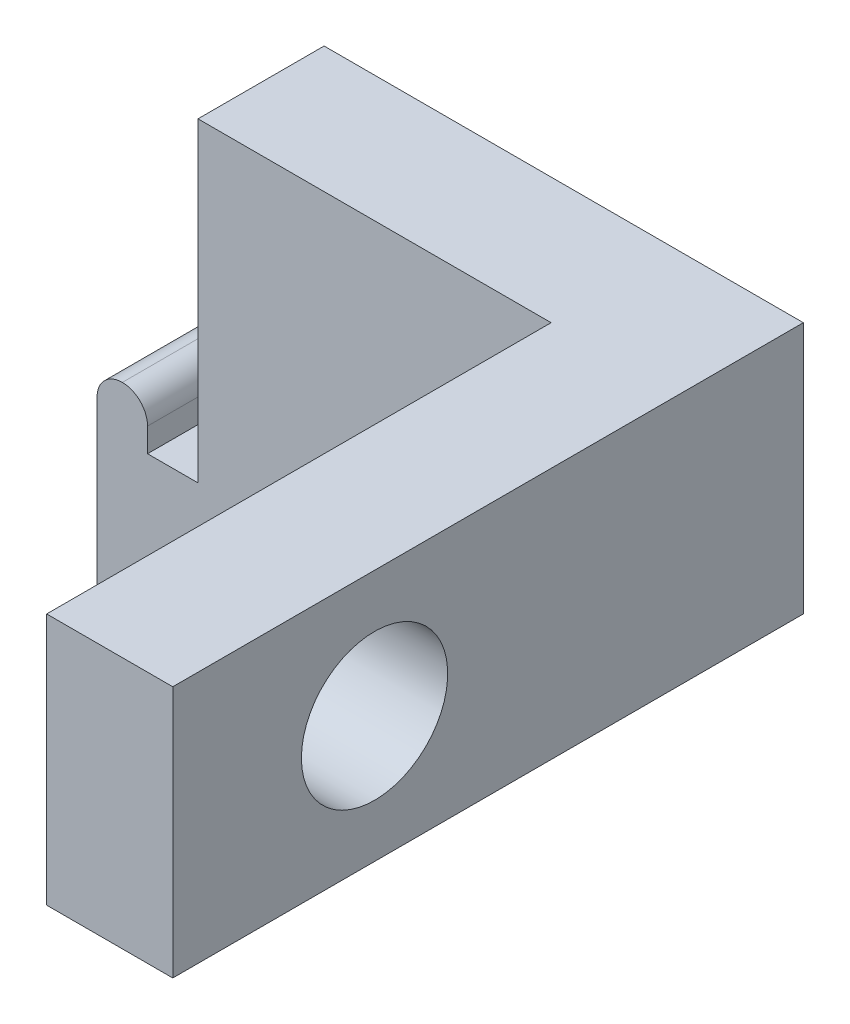
SolidWorks part; units mm, degrees
ref_plane "Front Plane" through (0, 0, 0) normal (0, 0, 1) x (1, 0, 0)
ref_plane "Top Plane" through (0, 0, 0) normal (0, 1, 0) x (1, 0, 0)
ref_plane "Right Plane" through (0, 0, 0) normal (1, 0, 0) x (0, 0, -1)
sketch "Sketch1" plane through (0, 0, 0) normal (0, 1, 0) x (1, 0, 0)
  line L0 (0, 0) -> (0, 31.75)
  line L1 (0, 31.75) -> (-22.86, 31.75)
  line L2 (-22.86, 31.75) -> (-22.86, 25.4)
  line L3 (-22.86, 25.4) -> (-6.35, 25.4)
  line L4 (-6.35, 25.4) -> (-6.35, 0)
  line L5 (-6.35, 0) -> (0, 0)
  dimension "D1" = 25.4
  dimension "D2" = 16.51
  dimension "D3" = 6.35
  dimension "D4" = 6.35
extrude "Boss-Extrude1" add sketch "Sketch1" along normal blind 12.7
sketch "Sketch2" plane through (-6.35, 0, 0) normal (-1, 0, 0) x (0, 0, 1)
  line L0 (0, 12.7) -> (0, 0) construction
  line L1 (-25.4, 12.7) -> (-25.4, 0) construction
  circle A0 centre (-10.16, 6.35) radius 3.683
  point P2 (0, 0)
  point P5 (0, 6.35)
  point P8 (-25.4, 6.35)
  dimension "D1" = 7.366
  dimension "D2" = 15.24
extrude "Cut-Extrude1" cut sketch "Sketch2" against normal blind 12.7
sketch "Sketch3" plane through (0, 0, -31.75) normal (0, 0, -1) x (-1, 0, 0)
  line L0 (22.86, 12.7) -> (24.13, 12.7)
  line L3 (29.21, -0.6985) -> (29.21, -12.0015)
  line L5 (17.78, -12.0015) -> (17.78, 0)
  line L6 (0, 0) -> (22.86, 0) construction
  line L7 (17.78, 0) -> (22.86, 0)
  line L8 (22.86, 0) -> (22.86, 12.7)
  line L9 (17.78, -12.0015) -> (24.13, -12.0015)
  line L10 (24.13, -12.0015) -> (24.13, -9.525)
  line L11 (24.13, -9.525) -> (26.67, -9.525)
  line L12 (26.67, -9.525) -> (26.67, -12.0015)
  line L13 (26.67, -12.0015) -> (29.21, -12.0015)
  line L15 (24.13, 12.7) -> (24.13, -3.175)
  line L16 (24.13, -3.175) -> (26.67, -3.175)
  line L17 (26.67, -3.175) -> (26.67, -0.6985)
  line L18 (26.67, -0.6985) -> (29.21, -0.6985)
  line L19 (26.67, -9.525) -> (26.67, -3.175) construction
  point P3 (26.67, -6.35)
  point P4 (29.21, -6.35)
  point P17 (22.86, 6.35)
  point P22 (35.9101, 2.4765)
  dimension "D1" = 2.54
  dimension "D2" = 11.303
  dimension "D3" = 6.35
  dimension "D4" = 12.7
  dimension "D5" = 2.54
  dimension "D6" = 17.78
  dimension "D7" = 6.35
extrude "Boss-Extrude2" add sketch "Sketch3" against normal blind 6.35
fillet "Fillet1" radius 1.27 1 edges at (-26.67, -0.6985, -28.575)
fillet "Fillet2" radius 1.27 3 edges at (-26.67, -12.0015, -28.575) (-29.21, -12.0015, -28.575) (-29.21, -0.6985, -28.575)
